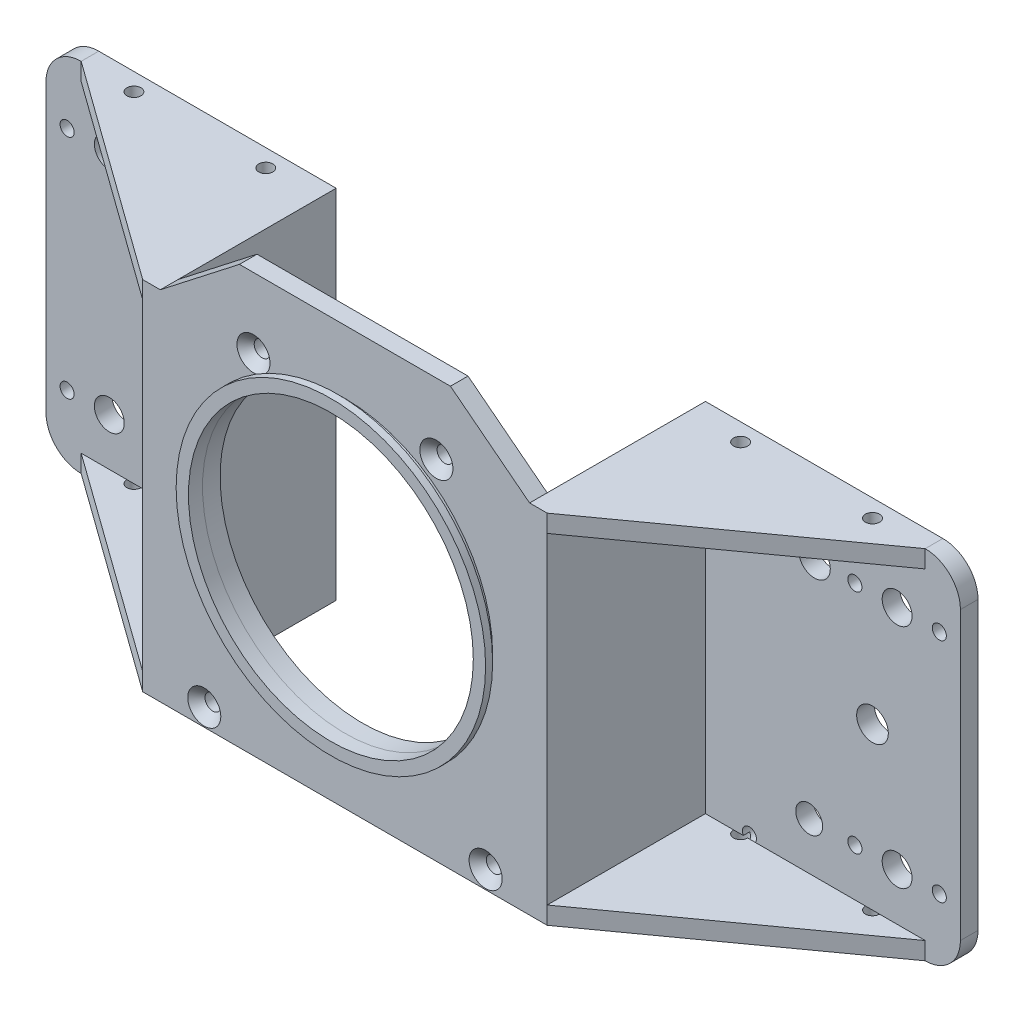
SolidWorks part; units mm, degrees
other "Markierung1"
sketch "Skizze14" plane through (-55, -59, -35.3553) normal (-0.9111, -0.4064, -0.0681) x (-0.4067, 0.9135, -0.0111)
ref_plane "Ebene vorne" through (0, 0, 0) normal (0, 0, 1) x (1, 0, 0)
ref_plane "Ebene oben" through (0, 0, 0) normal (0, 1, 0) x (1, 0, 0)
ref_plane "Ebene rechts" through (0, 0, 0) normal (1, 0, 0) x (0, 0, -1)
sketch "Skizze1" plane through (0, 0, 0) normal (0, 0, 1) x (1, 0, 0)
  line L10 (-52.5, -59) -> (52.5, -59)
  line L12 (30, 60) -> (-30, 60)
  line L13 (0, -32.7236) -> (0, 32.7236) construction
  line L16 (32.7236, 0) -> (-32.7236, 0) construction
  line L18 (30, 60) -> (52.5, 42.5)
  line L19 (52.5, -59) -> (52.5, 42.5)
  line L21 (-52.5, -59) -> (-52.5, 42.5)
  line L22 (-30, 60) -> (-52.5, 42.5)
  circle A1 centre (26, 40) radius 2.25
  circle A2 centre (-26, 40) radius 2.25
  circle A3 centre (0, 0) radius 40.5
  circle A4 centre (40, -54) radius 2.25
  circle A5 centre (-40, -54) radius 2.25
  point P4 (0, 60)
  dimension "D1" = 81
  dimension "D2" = 4.5
  dimension "D3" = 4.5
  dimension "D8" = 4.5
  dimension "D4" = 30
  dimension "D5" = 59
  dimension "D6" = 40
  dimension "D7" = 5
extrude "Aufsatz-Linear austragen1" add sketch "Skizze1" along normal blind 5
ref_axis "Achse1" through (0, 0, -37.8731) along (0, 0, 1)
ref_plane "Ebene1" through (0, 60, 0) normal (0, 1, 0) x (1, 0, 0)
sketch "Sketch5" plane through (0, 0, 5) normal (0, 0, 1) x (1, 0, 0)
  line L1 (52.5, 42.5) -> (57.5, 42.5)
  line L2 (52.5, 42.5) -> (52.5, -59)
  line L3 (52.5, -59) -> (57.5, -59)
  line L4 (57.5, 42.5) -> (57.5, -59)
  dimension "D1" = 5
  dimension "D2" = 0
  dimension "D3" = 101.5
extrude "Boss-Extrude1" add sketch "Sketch5" against normal blind 50
sketch "Skizze15" plane through (0, 0, -45) normal (0, 0, 1) x (1, 0, 0)
  line L0 (57.5, 42.5) -> (120, 42.5)
  line L2 (57.5, -59) -> (57.5, 42.5)
  line L4 (130, -49) -> (130, 32.5)
  line L12 (57.5, -59) -> (120, -59)
  line L22 (0, -55) -> (0, 55) construction
  line L23 (57.5, -59) -> (57.5, 42.5) construction
  line L24 (52.5, -59) -> (57.5, -59) construction
  arc A0 (120, -59) -> (130, -49) centre (120, -49) ccw
  arc A1 (120, 42.5) -> (130, 32.5) centre (120, 32.5) cw
  circle A2 centre (112, 24) radius 4.25
  circle A5 centre (100, 24) radius 2
  circle A7 centre (124, 24) radius 2
  circle A10 centre (112, -40.5) radius 4.25
  circle A11 centre (100, -40.5) radius 2
  circle A12 centre (124, -40.5) radius 2
  dimension "D4" = 10
  dimension "D7" = 24
  dimension "D5" = 8.5
  dimension "D6" = 112
  dimension "D10" = 12
  dimension "D11" = 4
  dimension "D12" = 4
  dimension "D13" = 12
  dimension "D1" = 130
  dimension "D2" = 2
extrude "Aufsatz-Linear austragen2" add sketch "Skizze15" along normal blind 5
mirror "Spiegeln1" about plane through (0, 0, 0) normal (1, 0, 0) of "Aufsatz-Linear austragen2", "Boss-Extrude1"
sketch "Sketch1" plane through (0, 0, -40) normal (0, 0, 1) x (1, 0, 0)
  line L0 (0, -27.5) -> (0, 27.5) construction
  line L1 (57.5, -59) -> (120, -59) construction
  line L2 (27.5, 0) -> (-27.5, 0) construction
  line L5 (52.5, 42.5) -> (52.5, -59) construction
  line L6 (120, 42.5) -> (52.5, 42.5) construction
  line L8 (52.5, -59) -> (120, -59) construction
  circle A0 centre (105, -8.25) radius 4.5
  circle A1 centre (87, -40.5) radius 3.8198
  circle A2 centre (112, -40.5) radius 4.25 construction
  circle A3 centre (88.5, 24) radius 4.5
  circle A4 centre (70, -53) radius 2
  circle A5 centre (112, 24) radius 4.25 construction
  circle A6 centre (70, 36.5) radius 2
  dimension "D1" = 9
  dimension "D2" = 105
  dimension "D3" = 8.25
  dimension "D4" = 9
  dimension "D5" = 24
  dimension "D6" = 23.5
  dimension "D7" = 25
  dimension "D8" = 18.5
  dimension "D9" = 6
  dimension "D10" = 17.5
  dimension "D11" = 17.5
  dimension "D12" = 6
  dimension "D13" = 4
  dimension "D14" = 4
extrude "Cut-Extrude1" cut sketch "Sketch1" against normal through all both and the other way through all
sketch "Sketch6" plane through (0, -59, 0) normal (0, -1, 0) x (1, 0, 0)
  line L0 (57.5, 5) -> (120, -40)
  line L1 (120, -40) -> (57.5, -40)
  line L2 (57.5, -40) -> (57.5, 5)
extrude "Boss-Extrude2" add sketch "Sketch6" against normal blind 5
sketch "Sketch11" plane through (0, -59, 0) normal (0, -1, 0) x (1, 0, 0)
  line L0 (52.5, -45) -> (120, -45) construction
  line L1 (120, -40) -> (120, -45) construction
  circle A0 centre (105, -40) radius 2
  circle A1 centre (67.5, -40) radius 2
  dimension "D1" = 5
  dimension "D2" = 5
  dimension "D3" = 15
  dimension "D4" = 37.5
  dimension "D5" = 4
  dimension "D6" = 4
extrude "Cut-Extrude2" cut sketch "Sketch11" against normal blind 5
mirror "Mirror1" about plane through (0, 0, 0) normal (1, 0, 0) of "Boss-Extrude2", "Cut-Extrude2"
pattern_linear "LPattern1" count 2 spacing 96.5 along (0, 1, 0) of "Mirror1"
sketch "Sketch9" plane through (0, 0, 5) normal (0, 0, 1) x (1, 0, 0)
  circle A0 centre (0, 0) radius 40.5
  circle A1 centre (0, 0) radius 44
  dimension "D1" = 88
extrude "Boss-Extrude3" add sketch "Sketch9" along normal blind 4 separate body
sketch "Sketch13" plane through (0, 0, 5) normal (0, 0, 1) x (1, 0, 0)
  circle A0 centre (0, 0) radius 44
  circle A1 centre (0, 0) radius 42
  dimension "D1" = 88
  dimension "D2" = 84
extrude "Cut-Extrude3" cut sketch "Sketch13" along normal blind 2
hole_wizard "CSK for M4 Flat Head Machine Screw1" positions "Sketch14" profile "Sketch15" countersink size "M4" standard "ANSI Metric" end condition through all
sketch "Sketch14" plane through (0, 0, 5) normal (0, 0, 1) x (1, 0, 0)
  point P0 (-26, 40)
  point P3 (26, 40)
  point P6 (40, -54)
  point P9 (-40, -54)
sketch "Sketch15" plane through (-26, 40, 5) normal (1, 0, 0) x (0, -1, 0)
  line L0 (0, 0) -> (0, 50)
  line L1 (0, 50) -> (2.25, 50)
  line L2 (2.25, 50) -> (2.25, 2.45)
  line L3 (2.25, 2.45) -> (4.7, 0)
  line L5 (4.7, 0) -> (0, 0)
  line L6 (-2.25, 2.45) -> (-4.7, 0) construction
  line L11 (0, -6.35) -> (0, 107.95) construction
  dimension "Thru Hole Dia." = 4.5
  dimension "Thru Hole Depth" = 50
  dimension "Near C'Sink Dia." = 9.4
  dimension "Near C'Sink Angle" = 90
